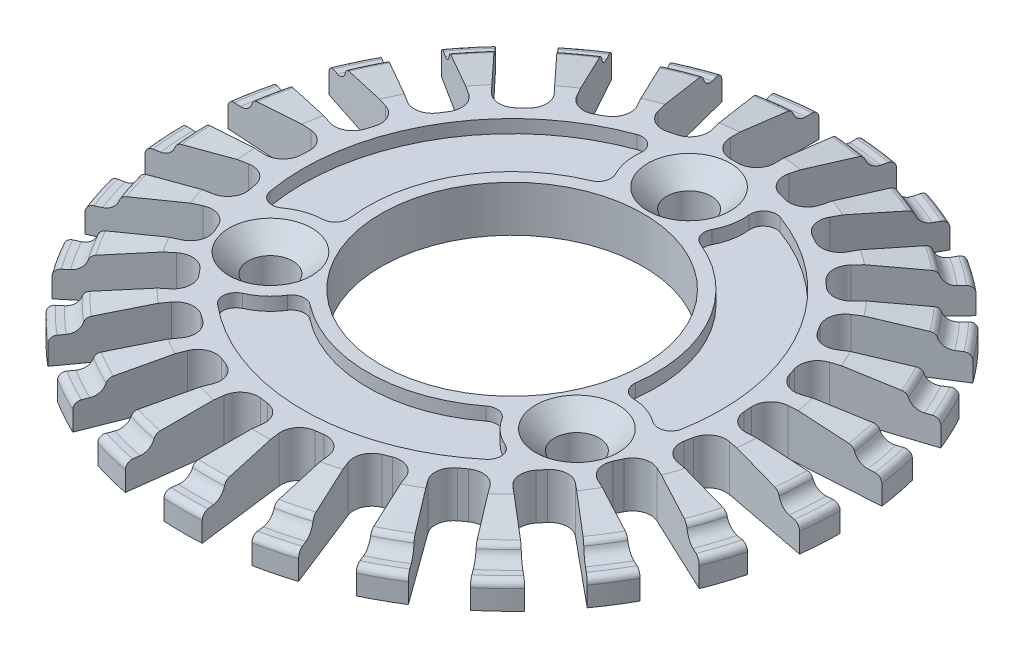
SolidWorks part; units mm, degrees
material "Nylon PA12"
ref_plane "Front Plane" through (0, 0, 0) normal (0, 0, 1) x (1, 0, 0)
ref_plane "Top Plane" through (0, 0, 0) normal (0, 1, 0) x (1, 0, 0)
ref_plane "Right Plane" through (0, 0, 0) normal (1, 0, 0) x (0, 0, -1)
sketch "Sketch1" plane through (0, 0, 0) normal (0, 1, 0) x (1, 0, 0)
  circle A0 centre (0, 0) radius 25.15
  circle A1 centre (0, 0) radius 22.5 construction
  circle A2 centre (0, 0) radius 27.5 construction
  dimension "D1" = 50.3
  dimension "D2" = 55
  dimension "D3" = 5
extrude "Boss-Extrude1" add sketch "Sketch1" along normal blind 2
sketch "Sketch2" plane through (0, 2, 0) normal (0, 1, 0) x (1, 0, 0)
  circle A0 centre (0, 0) radius 23.15
  circle A1 centre (0, 0) radius 25.15 construction
  dimension "D1" = 2
extrude "Boss-Extrude2" add sketch "Sketch2" along normal blind 1.5
fillet "Fillet1" radius 1 1 edges at (0, 2, 23.15)
fillet "Fillet2" radius 0.5 1 edges at (0, 2, 25.15)
chamfer "Chamfer1" distance 0.5 distance2 4 1 edges at (0, 3.5, 23.15) first distance on face at (0, 3, 23.15)
fillet "Fillet3" radius 0.5 1 edges at (0, 3, 23.15)
sketch "Sketch3" plane through (0, 3.5, 0) normal (0, 1, 0) x (1, 0, 0)
  line L0 (0, 0) -> (0, 44.4477) construction
  line L2 (-1.695, 17) -> (1.695, 17) construction
  line L3 (-1.695, 17) -> (-1.695, 27.5)
  line L4 (-1.695, 27.5) -> (1.695, 27.5)
  line L5 (1.695, 17) -> (1.695, 27.5)
  circle A0 centre (0, 44.4477) radius 27.5 construction
  arc A1 (1.695, 17) -> (-1.695, 17) centre (0, 44.4477) cw
  point P7 (0, 27.5)
  dimension "D4" = 55
  dimension "D1" = 27.5
  dimension "D2" = 3.39
  dimension "D3" = 10.5
sketch "Sketch4" plane through (0, 2, 0) normal (0, 1, 0) x (1, 0, 0)
  line L0 (0, 0) -> (0, 44.4477) construction
  line L1 (-1.695, 27.5) -> (1.695, 27.5) construction
  line L2 (1.695, 17) -> (1.695, 27.5) construction
  line L3 (-1.695, 17) -> (-1.695, 27.5) construction
  line L4 (0, 0) -> (0, 44.4477) construction
  line L5 (-1.695, 27.5) -> (1.695, 27.5)
  line L6 (1.695, 17) -> (1.695, 27.5)
  line L7 (-1.695, 17) -> (-1.695, 27.5)
  circle A0 centre (0, 44.4477) radius 27.5 construction
  arc A1 (-1.695, 17) -> (1.695, 17) centre (0, 44.4477) ccw construction
  circle A2 centre (0, 44.4477) radius 27.5 construction
  arc A3 (-1.695, 17) -> (1.695, 17) centre (0, 44.4477) ccw
extrude "Cut-Extrude1" cut sketch "Sketch4" against normal through all and the other way blind 2
fillet "Fillet4" radius 1.4 2 edges at (1.695, 1.75, -17) (-1.695, 1.75, -17)
ref_axis "Axis1" through (0, 1.5, 0) along (0, -1, 0)
pattern_circular "CirPattern1" count 25 over 360 about axis through (0, 1.5, 0) along (0, -1, 0) of "Cut-Extrude1", "Fillet4"
sketch "Sketch5" plane through (0, 3.5, 0) normal (0, 1, 0) x (1, 0, 0)
  circle A0 centre (0, 0) radius 10
  dimension "D1" = 20
extrude "Cut-Extrude2" cut sketch "Sketch5" against normal through all
sketch "Sketch6" plane through (0, 3.5, 0) normal (0, 1, 0) x (1, 0, 0)
  line L0 (0, 0) -> (0, 25.9825) construction
  point P3 (0, 13.5)
  dimension "D1" = 13.5
hole_wizard "CSK for M3 Countersunk Flat Head Screw1" positions "Sketch7" profile "Sketch8" countersink size "M3" standard "DIN"
sketch "Sketch7" plane through (0, 3.5, 0) normal (0, 1, 0) x (1, 0, 0)
  point P0 (0, 13.5)
sketch "Sketch8" plane through (0, 3.5, -13.5) normal (1, 0, 0) x (0, 0, 1)
  line L0 (0, 0) -> (0, 13.0215)
  line L1 (0, 13.0215) -> (1.7, 12)
  line L2 (1.7, 12) -> (1.7, 1.45)
  line L3 (1.7, 1.45) -> (3.15, 0)
  line L5 (3.15, 0) -> (0, 0)
  line L6 (-1.7, 1.45) -> (-3.15, 0) construction
  line L10 (0, 13.0215) -> (-1.7, 12) construction
  line L11 (0, -6.35) -> (0, 107.95) construction
  dimension "Hole Dia." = 3.4
  dimension "Hole Depth" = 12
  dimension "Near C'Sink Dia." = 6.3
  dimension "Near C'Sink Angle" = 90
  dimension "Drill Angle" = 118
pattern_circular "CirPattern2" count 3 over 360 about axis through (0, 1.5, 0) along (0, -1, 0) of "CSK for M3 Countersunk Flat Head Screw1"
sketch "Sketch9" plane through (0, 3.5, 0) normal (0, 1, 0) x (1, 0, 0)
  circle A0 centre (-11.6913, -6.75) radius 4.15 construction
  circle A1 centre (0, 13.5) radius 4.15 construction
  circle A2 centre (0, 0) radius 11 construction
  circle A3 centre (0, 0) radius 10 construction
  circle A4 centre (0, 0) radius 17.9537 construction
  circle A6 centre (0, 0) radius 15.9537 construction
  arc A7 (-3.6147, 15.5388) -> (-15.2643, -4.639) centre (0, 0) ccw
  arc A8 (-2.9623, 10.5936) -> (-10.6555, -2.7314) centre (0, 0) ccw
  arc A9 (-3.6147, 15.5388) -> (-2.9623, 10.5936) centre (0, 13.5) ccw
  arc A10 (-15.2643, -4.639) -> (-10.6555, -2.7314) centre (-11.6913, -6.75) cw
  point P17 (-3.6147, 15.5388)
  point P18 (-15.2643, -4.639)
  point P19 (-10.6555, -2.7314)
  point P20 (-2.9623, 10.5936)
  dimension "D1" = 8.3
  dimension "D2" = 8.3
  dimension "D3" = 1
  dimension "D4" = 2
  dimension "D5" = 31.9074
extrude "Cut-Extrude3" cut sketch "Sketch9" against normal blind 1
fillet "Fillet5" radius 1 4 edges at (-10.6555, 3, 2.7314) (-15.2643, 3, 4.639) (-2.9623, 3, -10.5936) (-3.6147, 3, -15.5388)
pattern_circular "CirPattern3" count 3 over 360 about axis through (0, 1.5, 0) along (0, -1, 0) of "Fillet5", "Cut-Extrude3"
equation "\"D1@Sketch1\"=\"D2@Sketch1\"-4.7"
